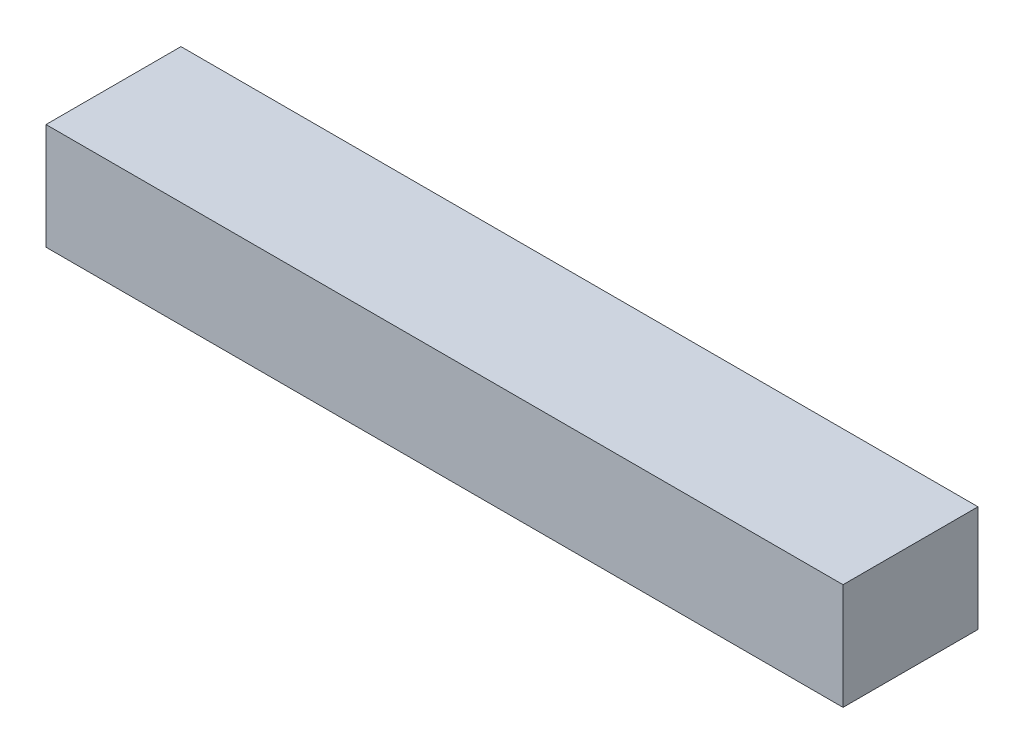
SolidWorks part; units mm, degrees
ref_plane "Front Plane" through (0, 0, 0) normal (0, 0, 1) x (1, 0, 0)
ref_plane "Top Plane" through (0, 0, 0) normal (0, 1, 0) x (1, 0, 0)
ref_plane "Right Plane" through (0, 0, 0) normal (1, 0, 0) x (0, 0, -1)
sketch "Sketch1" plane through (0, 0, 0) normal (0, 1, 0) x (1, 0, 0)
  line L1 (-37.5, -6.35) -> (37.5, -6.35)
  line L2 (-37.5, -6.35) -> (-37.5, 6.35)
  line L3 (-37.5, 6.35) -> (37.5, 6.35)
  line L4 (37.5, -6.35) -> (37.5, 6.35)
  line L5 (-37.5, -6.35) -> (37.5, 6.35) construction
  line L6 (-37.5, 6.35) -> (37.5, -6.35) construction
  point P0 (0, 0)
  dimension "D1" = 12.7
  dimension "D2" = 75
extrude "Boss-Extrude1" add sketch "Sketch1" along normal blind 10
